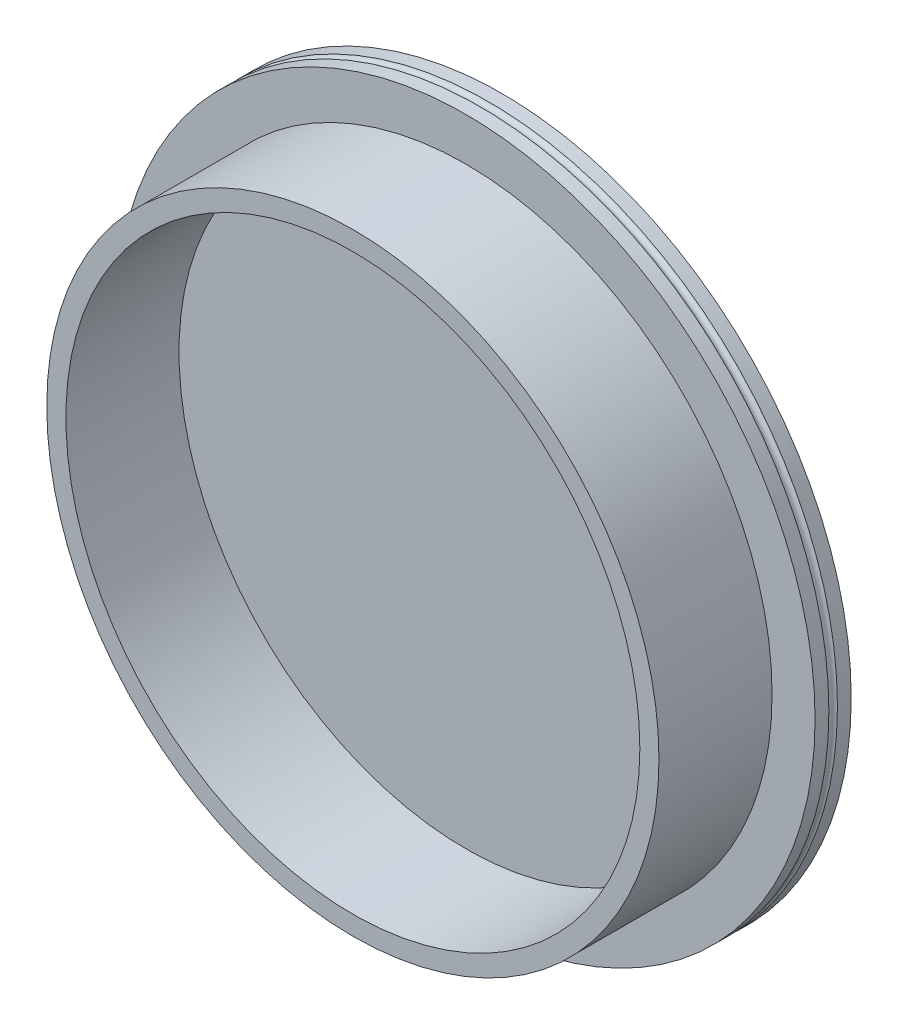
SolidWorks part; units mm, degrees
ref_plane "Front" through (0, 0, 0) normal (0, 0, 1) x (1, 0, 0)
ref_plane "Top" through (0, 0, 0) normal (0, 1, 0) x (1, 0, 0)
ref_plane "Right" through (0, 0, 0) normal (1, 0, 0) x (0, 0, -1)
ref_axis "Axis1" through (0, 0, -80.9) along (0, 0, 1)
sketch "Sketch1" plane through (0, 0, 0) normal (1, 0, 0) x (0, 0, -1)
  line L0 (-12, 0) -> (0, 0) construction
  line L4 (-4.5858, 115.875) -> (0, 115.875)
  line L6 (0, 113.375) -> (-2, 113.375)
  line L7 (-12, 101.6) -> (-12, 115.875)
  line L8 (-2, 113.375) -> (-2, 107.375)
  line L9 (-12, 115.875) -> (-7.4142, 115.875)
  line L10 (-2, 107.375) -> (0, 107.375)
  line L11 (0, 115.875) -> (0, 113.375)
  line L12 (0, 107.375) -> (0, 0)
  line L13 (0, 0) -> (-12, 0)
  line L14 (-12, 101.6) -> (-49.5385, 101.6)
  line L15 (-49.5385, 101.6) -> (-49.5385, 95.25)
  line L16 (-49.5385, 95.25) -> (-12, 95.25)
  line L17 (-12, 95.25) -> (-12, 0)
  arc A0 (-7.4142, 115.875) -> (-4.5858, 115.875) centre (-6, 116.375) ccw
  dimension "D6" = 3
  dimension "D9" = 1
  dimension "D4" = 231.75
  dimension "D5" = 12
  dimension "D8" = 6.35
  dimension "D10" = 214.75
  dimension "D11" = 6
  dimension "D12" = 2
  dimension "D13" = 95.25
revolve "Base-Revolve" add sketch "Sketch1" angle 360 about L0
sketch "Sketch2" [suppressed] plane through (0, 0, 0) normal (0, 0, -1) x (-1, 0, 0)
  line L1 (79.5782, 49.0982) -> (-79.5782, 49.0982)
  line L2 (85.9282, 42.7482) -> (85.9282, -42.7482)
  line L3 (79.5782, -49.0982) -> (-79.5782, -49.0982)
  line L4 (-85.9282, 42.7482) -> (-85.9282, -42.7482)
  arc A0 (85.9282, 42.7482) -> (79.5782, 49.0982) centre (79.5782, 42.7482) ccw
  arc A1 (79.5782, -49.0982) -> (85.9282, -42.7482) centre (79.5782, -42.7482) ccw
  arc A2 (-85.9282, -42.7482) -> (-79.5782, -49.0982) centre (-79.5782, -42.7482) ccw
  arc A3 (-79.5782, 49.0982) -> (-85.9282, 42.7482) centre (-79.5782, 42.7482) ccw
  dimension "D1" = 6.35
